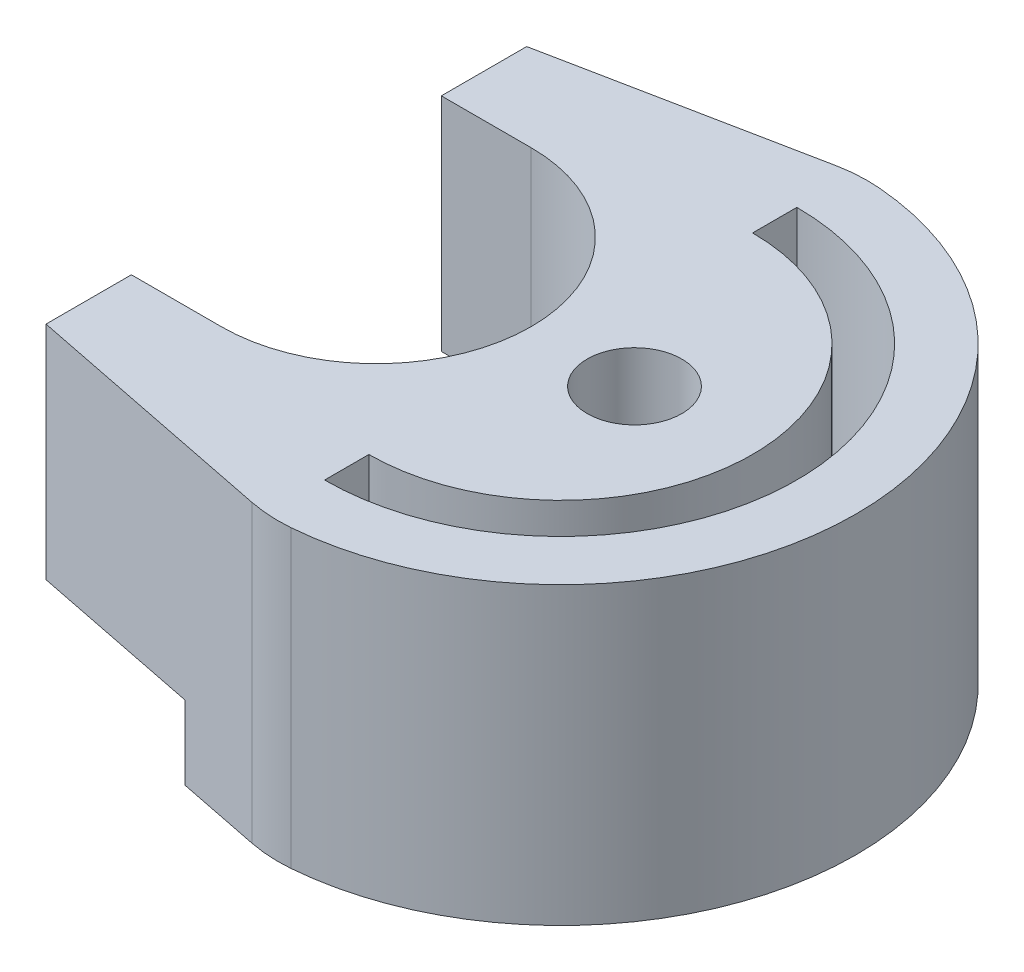
SolidWorks part; units mm, degrees
ref_plane "Front Plane" through (0, 0, 0) normal (0, 0, 1) x (1, 0, 0)
ref_plane "Top Plane" through (0, 0, 0) normal (0, 1, 0) x (1, 0, 0)
ref_plane "Right Plane" through (0, 0, 0) normal (1, 0, 0) x (0, 0, -1)
sketch "Sketch1" plane through (0, 0, 0) normal (0, 1, 0) x (1, 0, 0)
  line L0 (-0.1139, 1.9772) -> (-1.25, 1.7502)
  line L1 (-0.1139, -1.9772) -> (-1.25, -1.7502)
  line L2 (-0.6819, 1.25) -> (-0.6819, 0.8831)
  line L3 (-0.6819, -1.25) -> (-0.6819, -0.8831)
  line L4 (-1.25, -1.7502) -> (-4.1832, -1.1642)
  line L5 (-1.25, 1.7502) -> (-4.1832, 1.1642)
  line L6 (-1.859, 1.6286) -> (-1.859, -1.6286) construction
  line L7 (-1.25, 1.05) -> (-1.859, 1.05)
  line L8 (0, 1.6) -> (0, 1.3)
  line L9 (0, -1.3) -> (0, -1.6)
  line L10 (-1.25, 1.25) -> (-0.6819, 1.25)
  line L11 (-1.25, -1.25) -> (-0.6819, -1.25)
  line L12 (-0.6819, -1.25) -> (-0.6819, -1.8637)
  line L13 (-0.6819, 1.8637) -> (-0.6819, -1.8637) construction
  line L14 (-0.6819, 1.25) -> (-0.6819, 1.8637)
  line L15 (-1.859, 1.05) -> (-1.859, 1.6286)
  line L16 (-1.25, -1.05) -> (-1.859, -1.05)
  line L17 (-4.25, 0.8) -> (-3.75, 0.8)
  line L18 (-4.25, 0.8) -> (-4.25, -0.8)
  line L19 (-4.25, -0.8) -> (-3.75, -0.8)
  line L20 (-3.75, 0.8) -> (-3.75, -0.8)
  line L21 (-1.859, -1.05) -> (-1.859, -1.6286)
  line L22 (-1.859, 1.05) -> (-1.859, 0.8553)
  line L23 (-1.859, -1.05) -> (-1.859, -0.8553)
  circle A0 centre (-1.25, 0) radius 1.25
  circle A1 centre (-1.25, 0) radius 1.05
  arc A2 (0.1641, 1.9933) -> (0.1641, -1.9933) centre (0, 0) cw
  arc A3 (-0.1139, -1.9772) -> (0.1641, -1.9933) centre (0.0821, -0.9966) ccw
  arc A4 (-4.7783, 0.7954) -> (-4.7783, -0.7954) centre (-3.75, 0) ccw
  arc A5 (0.1641, 1.9933) -> (-0.1139, 1.9772) centre (0.0821, 0.9966) ccw
  arc A6 (-4.1832, 1.1642) -> (-4.7783, 0.7954) centre (-3.9873, 0.1835) ccw
  arc A7 (-4.1832, -1.1642) -> (-4.7783, -0.7954) centre (-3.9873, -0.1835) cw
  circle A8 centre (-3, 0) radius 0.3207
  circle A9 centre (0.5, 0) radius 0.3207
  arc A10 (0, 1.6) -> (0, -1.6) centre (0, 0) cw
  arc A11 (0, 1.3) -> (0, -1.3) centre (0, 0) cw
  point P12 (-3, 0)
  point P20 (0.5, 0)
extrude "Boss-Extrude4" add sketch "Sketch1" along normal blind 2 contours A2 A5 L0 L14 L2 A0 L3 L12 L1 A3 A11 L8 A10 L9 A9 region at (0.0273, 0, -1.947)
extrude "Boss-Extrude5" add sketch "Sketch1<30>" along normal blind 1.5 from offset 0.5 contours A1 L2 A0 L15 L7 | A1 L3 A0 L2 | A1 L16 L21 A0 L3 | A0 L11 L3 | A0 L2 L10 | A0 L10 L14 L0 L5 L15 | A0 L21 L4 L1 L12 L11 region at (-1.2486, 0, -1.4875) region at (-0.8224, 0, -1.2095) region at (-0.2039, 0, -0.6407) region at (-1.1936, 0, -1.1131) region at (-1.2486, 0, 1.4875) region at (-1.1936, 0, 1.1131) region at (-0.8224, 0, 1.2095)
sketch "Sketch1<30>" plane through (0, 0, 0) normal (0, 1, 0) x (1, 0, 0) same geometry as "Sketch1"
